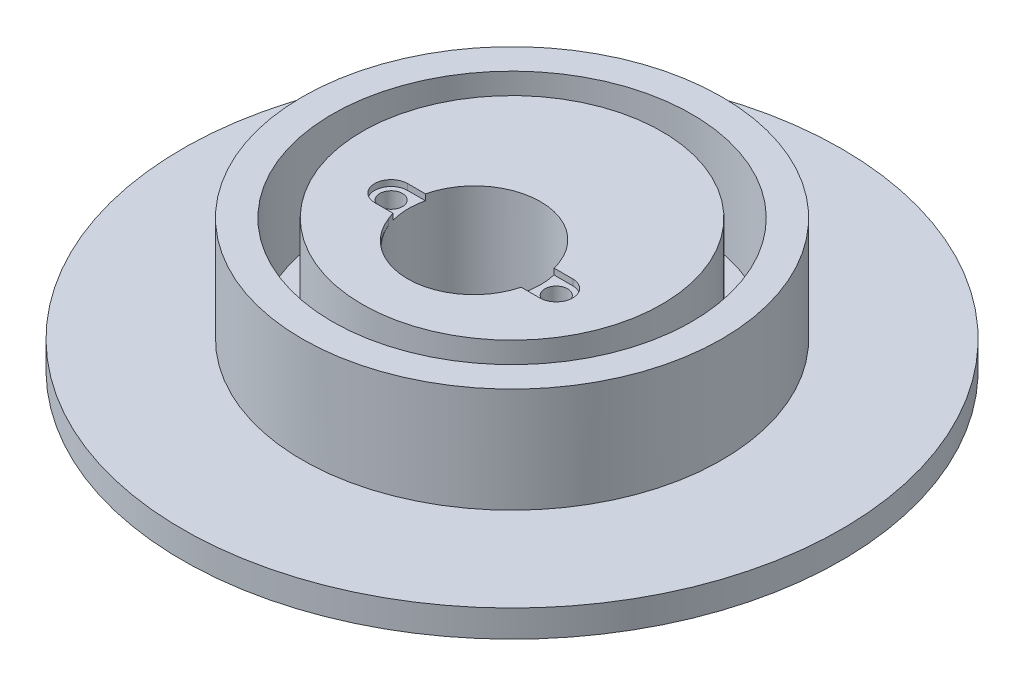
SolidWorks part; units mm, degrees
ref_plane "Front Plane" through (0, 0, 0) normal (0, 0, 1) x (1, 0, 0)
ref_plane "Top Plane" through (0, 0, 0) normal (0, 1, 0) x (1, 0, 0)
ref_plane "Right Plane" through (0, 0, 0) normal (1, 0, 0) x (0, 0, -1)
sketch "Sketch2" plane through (0, 0, 0) normal (0, 1, 0) x (1, 0, 0)
  circle A1 centre (0, 0) radius 4.4958 construction
  circle A2 centre (0, -8.001) radius 13.97 construction
  circle A4 centre (0, 0) radius 44.45
  circle A5 centre (0, 0) radius 38.1
  dimension "D1" = 8.001
  dimension "D2" = 27.94
  dimension "D3" = 8.9916
  dimension "D4" = 88.9
  dimension "D5" = 76.2
extrude "Boss-Extrude1" add sketch "Sketch2" along normal blind 6.35 contours A5 | A4 A5 region at (-43.1928, 0, 0) region at (0, 0, 0)
extrude "Boss-Extrude2" add sketch "Sketch2<3>" along normal blind 27.94
sketch "Sketch2<3>" plane through (0, 0, 0) normal (0, 1, 0) x (1, 0, 0) same geometry as "Sketch2"
sketch "Sketch3" plane through (0, 6.35, 0) normal (0, 1, 0) x (1, 0, 0)
  line L0 (0, -8.0001) -> (0, -0.0001)
  line L1 (0, -0.0001) -> (-4.5, -0.0001) construction
  line L2 (-13.5274, -4.5001) -> (-17.4719, -4.5001)
  line L3 (-17.4719, -11.5001) -> (-13.5274, -11.5001)
  line L4 (13.5835, -11.5001) -> (17.5281, -11.5001)
  line L5 (17.5281, -4.5001) -> (13.5835, -4.5001)
  circle A0 centre (0, 0) radius 31.75
  arc A1 (13.5835, -4.5001) -> (-13.5274, -4.5001) centre (0.0281, -8.0001) ccw
  arc A2 (-17.4719, -4.5001) -> (-17.4719, -11.5001) centre (-17.4719, -8.0001) ccw
  arc A3 (-13.5274, -11.5001) -> (13.5835, -11.5001) centre (0.0281, -8.0001) ccw
  arc A4 (17.5281, -11.5001) -> (17.5281, -4.5001) centre (17.5281, -8.0001) ccw
  arc A5 (-13.5274, -4.5001) -> (-13.5274, -11.5001) centre (0.0281, -8.0001) ccw
  arc A6 (13.5835, -4.5001) -> (13.5835, -11.5001) centre (0.0281, -8.0001) cw
  dimension "D1" = 63.5
extrude "Boss-Extrude4" add sketch "Sketch3" along normal blind 21.59 contours L5 A6 L4 A4 | A5 L2 A2 L3 | A0 A4 L4 A3 L3 A2 L2 A1 L5 region at (-17.0691, 6.35, 8.0001) region at (17.1253, 6.35, 8.0001) region at (-30.852, 6.35, 0)
sketch "Sketch4" plane through (0, 27.94, 0) normal (0, 1, 0) x (1, 0, 0)
  line L0 (0.1313, -8.2627) -> (0.1313, -0.2627)
  line L1 (0.1313, -0.2627) -> (-4.3687, -0.2627) construction
  line L2 (-13.4241, -4.7627) -> (-17.3687, -4.7627)
  line L3 (-17.3687, -11.7627) -> (-13.4241, -11.7627)
  line L4 (13.6868, -11.7627) -> (17.6313, -11.7627)
  line L5 (17.6313, -4.7627) -> (13.6868, -4.7627)
  circle A0 centre (0.1313, -0.2626) radius 31.75 construction
  arc A1 (13.6868, -4.7627) -> (-13.4241, -4.7627) centre (0.1313, -8.2627) ccw
  arc A2 (-17.3687, -4.7627) -> (-17.3687, -11.7627) centre (-17.3687, -8.2627) ccw
  arc A3 (-13.4241, -11.7627) -> (13.6868, -11.7627) centre (0.1313, -8.2627) ccw
  arc A4 (17.6313, -11.7627) -> (17.6313, -4.7627) centre (17.6313, -8.2627) ccw
  circle A5 centre (-17.3687, -8.2627) radius 2.413
  circle A6 centre (17.6313, -8.2627) radius 2.413
  circle M8 centre (0.0281, -8.0001) radius 14
  dimension "D1" = 63.5
  dimension "D2" = 4.826
  dimension "D3" = 35
extrude "Cut-Extrude1" cut sketch "Sketch4" against normal blind 1.27 contours L2 A2 L3 A5 M8 | A5 | A6 | L4 A4 L5 A1 A3 A6 M8 region at (-14.0712, 27.94, 8.2733) region at (13.9978, 27.94, 10.5842) region at (-17.3687, 27.94, 8.2627) region at (17.6313, 27.94, 8.2627)
extrude "Cut-Extrude2" cut sketch "Sketch4<3>" against normal blind 8.89 contours A5 | A6 region at (-17.3687, 27.94, 8.2627) region at (17.6313, 27.94, 8.2627)
sketch "Sketch4<3>" plane through (0, 27.94, 0) normal (0, 1, 0) x (1, 0, 0) same geometry as "Sketch4"
sketch "Sketch5" plane through (0, 0, 0) normal (0, -1, 0) x (1, 0, 0)
  circle A0 centre (0, 0) radius 69.85
  dimension "D1" = 139.7
extrude "Boss-Extrude5" add sketch "Sketch5" against normal blind 5.715
